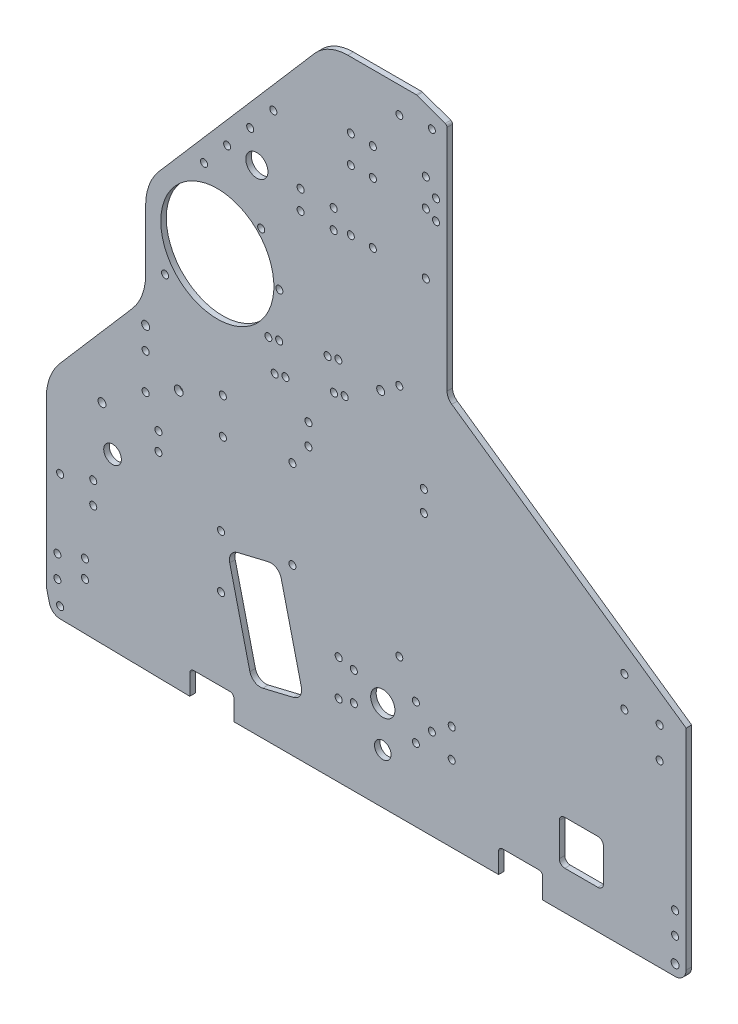
SolidWorks part; units mm, degrees
ref_plane "Front Plane" through (0, 0, 0) normal (0, 0, 1) x (1, 0, 0)
ref_plane "Top Plane" through (0, 0, 0) normal (0, 1, 0) x (1, 0, 0)
ref_plane "Right Plane" through (0, 0, 0) normal (1, 0, 0) x (0, 0, -1)
sketch "Sketch1" plane through (0, 0, 0) normal (0, 0, 1) x (1, 0, 0)
  line L0 (82.55, -20.32) -> (82.55, -6.35)
  line L2 (0, 0) -> (0, 157.48)
  line L4 (368.3, -20.32) -> (368.3, 106.68)
  line L5 (82.55, -6.35) -> (107.95, -6.35)
  line L6 (107.95, -6.35) -> (107.95, -20.32)
  line L7 (107.95, -20.32) -> (260.35, -20.32)
  line L8 (260.35, -20.32) -> (260.35, -6.35)
  line L9 (260.35, -6.35) -> (285.75, -6.35)
  line L10 (285.75, -6.35) -> (285.75, -20.32)
  line L11 (285.75, -20.32) -> (368.3, -20.32)
  line L12 (361.95, 12.7) -> (368.3, 12.7) construction
  line L13 (0, 0) -> (6.35, 0) construction
  line L14 (0.1896, -7.8901) -> (1.7771, -14.2401)
  line L15 (7.8295, -19.0491) -> (82.55, -20.32)
  line L16 (0, 0) -> (0, -6.35)
  line L17 (76.2, 128.905) -> (79.375, 128.905) construction
  line L18 (57.15, 118.5863) -> (101.6, 118.5862) construction
  line L19 (57.15, 118.5863) -> (57.15, 139.2238) construction
  line L20 (101.6, 118.5862) -> (101.6, 139.2237) construction
  line L21 (57.15, 139.2238) -> (101.6, 139.2237) construction
  line L22 (57.15, 118.5863) -> (101.6, 139.2237) construction
  line L23 (101.6, 118.5862) -> (57.15, 139.2238) construction
  line L25 (203.2, 59.805) -> (203.2, 194.805) construction
  line L26 (203.2, 194.805) -> (203.2, 329.805) construction
  line L27 (355.6, 332.105) -> (330.2, 332.105) construction
  line L28 (330.2, 332.105) -> (330.2, 217.805) construction
  line L29 (330.2, 217.805) -> (355.6, 217.805) construction
  line L30 (355.6, 217.805) -> (355.6, 332.105) construction
  line L31 (203.2, 344.805) -> (203.2, 194.805) construction
  line L32 (50.8, 332.105) -> (76.2, 332.105) construction
  line L33 (76.2, 332.105) -> (76.2, 217.805) construction
  line L34 (50.8, 217.805) -> (50.8, 332.105) construction
  line L35 (76.2, 217.805) -> (50.8, 217.805) construction
  line L36 (213.2, 344.805) -> (230.6638, 338.455)
  line L37 (203.2, 344.805) -> (161.925, 344.805)
  line L38 (203.2, 344.805) -> (213.2, 344.805)
  line L39 (348.5362, 344.805) -> (413.4623, 344.805)
  line L40 (348.5362, 344.805) -> (230.6638, 344.805) construction
  line L42 (161.925, 344.805) -> (0, 157.48)
  line L44 (230.6638, 338.455) -> (230.6638, 202.565)
  line L45 (230.6638, 202.565) -> (368.3, 106.68)
  line L46 (213.2, 344.805) -> (-141.0713, 344.805) construction
  circle A0 centre (6.35, 0) radius 2.032
  circle A1 centre (6.35, 12.7) radius 2.032
  circle A2 centre (361.95, 0) radius 2.032
  circle A3 centre (361.95, 12.7) radius 2.032
  arc A5 (1.7771, -14.2401) -> (7.8295, -19.0491) centre (7.9375, -12.7) ccw
  circle A6 centre (7.9375, -12.7) radius 2.032
  arc A7 (0, -6.35) -> (0.1896, -7.8901) centre (6.35, -6.35) ccw
  circle A8 centre (38.1, 78.105) radius 5.08
  circle A9 centre (76.2, 128.905) radius 2.54
  circle A10 centre (101.6, 118.5862) radius 2.032
  circle A11 centre (101.6, 139.2237) radius 2.032
  circle A12 centre (57.15, 139.2238) radius 2.032
  circle A13 centre (57.15, 118.5863) radius 2.032
  circle A15 centre (203.2, 59.805) radius 2
  circle A16 centre (203.2, 194.805) radius 2
  circle A17 centre (203.2, 329.805) radius 2
  circle A18 centre (63.5, 313.055) radius 2.032
  circle A20 centre (355.6, 332.105) radius 2.032
  circle A21 centre (330.2, 332.105) radius 2.032
  circle A22 centre (355.6, 217.805) radius 2.032
  circle A23 centre (330.2, 217.805) radius 2.032
  circle A24 centre (50.8, 332.105) radius 2.032
  circle A25 centre (76.2, 332.105) radius 2.032
  circle A26 centre (50.8, 217.805) radius 2.032
  circle A27 centre (76.2, 217.805) radius 2.032
  circle A28 centre (221.9319, 332.105) radius 2
  circle A29 centre (224.3138, 298.831) radius 2.032
  circle A30 centre (353.06, 100.7351) radius 2.032
  circle A31 centre (332.74, 115.9751) radius 2.032
  circle A32 centre (332.74, 98.1951) radius 2.032
  circle A33 centre (353.06, 82.9551) radius 2.032
  circle A34 centre (117.3562, 280.4276) radius 2.032
  circle A35 centre (104.0678, 265.0548) radius 2.032
  circle A36 centre (90.7795, 249.682) radius 2.032
  circle A38 centre (130.6445, 295.8004) radius 2.032
  circle A39 centre (68.326, 182.9237) radius 2.032
  circle A40 centre (224.3138, 287.401) radius 2.032
  point P82 (203.2, 344.805)
  point P83 (221.9319, 341.63)
  point P90 (368.3, 62.484)
  dimension "D6" = 4.064
  dimension "D10" = 6.35
  dimension "D11" = 4.064
  dimension "D17" = 38.1
  dimension "D27" = 4
  dimension "D31" = 4.064
  dimension "D32" = 41.275
  dimension "D36" = 4.064
  dimension "D47" = 39.624
  dimension "D48" = 4.064
  dimension "D25" = 5.08
  dimension "D26" = 4.064
  dimension "D52" = 4.064
  dimension "D65" = 4.064
  dimension "D69" = 10.16
  dimension "D2" = 127
  dimension "D3" = 13.97
  dimension "D4" = 25.4
  dimension "D5" = 152.4
  dimension "D7" = 12.7
  dimension "D8" = 6.35
  dimension "D9" = 20.32
  dimension "D12" = 12.7
  dimension "D13" = 1.5875
  dimension "D14" = 82.55
  dimension "D15" = 368.3
  dimension "D16" = 6.35
  dimension "D18" = 98.425
  dimension "D19" = 38.1
  dimension "D20" = 50.8
  dimension "D21" = 3.175
  dimension "D22" = 270
  dimension "D23" = 20.6375
  dimension "D24" = 44.45
  dimension "D28" = 135
  dimension "D29" = 12.7
  dimension "D30" = 15
  dimension "D33" = 63.5
  dimension "D34" = 27.4638
  dimension "D35" = 12.7
  dimension "D37" = 114.3
  dimension "D38" = 25.4
  dimension "D39" = 12.7
  dimension "D40" = 157.48
  dimension "D41" = 142.24
  dimension "D42" = 365.125
  dimension "D43" = 10
  dimension "D44" = 6.35
  dimension "D45" = 31.75
  dimension "D46" = 6.35
  dimension "D49" = 6.35
  dimension "D50" = 203.2
  dimension "D51" = 15.24
  dimension "D53" = 17.78
  dimension "D54" = 17.78
  dimension "D55" = 20.32
  dimension "D56" = 15.24
  dimension "D57" = 92.202
  dimension "D58" = 8.382
  dimension "D59" = 20.32
  dimension "D60" = 20.32
  dimension "D61" = 8.382
  dimension "D62" = 20.32
  dimension "D63" = 8.382
  dimension "D64" = 8.382
  dimension "D66" = 35.052
  dimension "D67" = 68.326
  dimension "D68" = 11.43
extrude "Boss-Extrude1" add sketch "Sketch1" along normal blind 3.175 contours L16 A7 L14 A5 L15 L2 A0 A1 A6 region at (171.4477, 119.565, 0)
fillet "Fillet1" radius 2.286 4 edges at (285.75, -6.35, 1.5875) (107.95, -6.35, 1.5875) (260.35, -6.35, 1.5875) (82.55, -6.35, 1.5875)
fillet "Fillet2" radius 6.35 1 edges at (230.6638, 202.565, 1.5875)
sketch "Sketch2" plane through (0, 0, 0) normal (0, 0, -1) x (-1, 0, 0)
  circle A0 centre (-100.5528, 71.086) radius 2.032 construction
  circle A1 centre (-100.5528, 40.606) radius 2.032 construction
  circle A2 centre (-22.225, 18.2025) radius 2.032 construction
  circle A3 centre (-22.225, 8.0425) radius 2.032 construction
  circle A4 centre (-100.5528, 71.086) radius 2.032
  circle A5 centre (-100.5528, 40.606) radius 2.032
  circle A6 centre (-22.225, 18.2025) radius 2.032
  circle A7 centre (-22.225, 8.0425) radius 2.032
extrude "Cut-Extrude1" cut sketch "Sketch2" against normal through all
fillet "Fillet3" radius 1.5875 2 edges at (230.6638, 338.455, 1.5875) (213.2, 344.805, 1.5875)
sketch "Sketch3" plane through (0, 0, 3.175) normal (0, 0, 1) x (1, 0, 0)
  line L0 (132.9524, 63.2646) -> (132.7215, 64.2281) construction
  line L1 (128.3814, 66.8897) -> (110.6828, 62.6472) construction
  line L2 (114.5132, 58.4237) -> (126.8822, 61.3887) construction
  line L3 (108.0212, 58.3071) -> (108.2522, 57.3436) construction
  line L4 (131.2006, 57.703) -> (140.0164, 20.9265) construction
  line L5 (144.0993, 16.7636) -> (132.9524, 63.2646) construction
  line L6 (108.2522, 57.3436) -> (119.3991, 10.8426) construction
  line L7 (121.1509, 16.4042) -> (112.3351, 53.1807) construction
  line L8 (119.3991, 10.8426) -> (119.6301, 9.8791) construction
  line L9 (144.3303, 15.8001) -> (144.0993, 16.7636) construction
  line L10 (137.8383, 15.6835) -> (125.4694, 12.7185) construction
  line L11 (123.9701, 7.2175) -> (141.6687, 11.4601) construction
  line L12 (132.9524, 63.2646) -> (132.7215, 64.2281)
  line L13 (128.3814, 66.8897) -> (110.6828, 62.6472)
  line L14 (114.5132, 58.4237) -> (126.8822, 61.3887)
  line L15 (108.0212, 58.3071) -> (108.2522, 57.3436)
  line L16 (131.2006, 57.703) -> (140.0164, 20.9265)
  line L17 (144.0993, 16.7636) -> (132.9524, 63.2646)
  line L18 (108.2522, 57.3436) -> (119.3991, 10.8426)
  line L19 (121.1509, 16.4042) -> (112.3351, 53.1807)
  line L20 (119.3991, 10.8426) -> (119.6301, 9.8791)
  line L21 (144.3303, 15.8001) -> (144.0993, 16.7636)
  line L22 (137.8383, 15.6835) -> (125.4694, 12.7185)
  line L23 (123.9701, 7.2175) -> (141.6687, 11.4601)
  line L24 (127.7894, 69.3598) -> (110.0908, 65.1172)
  line L25 (105.5512, 57.715) -> (105.7822, 56.7515)
  line L26 (105.7822, 56.7515) -> (116.9291, 10.2505)
  line L27 (116.9291, 10.2505) -> (117.16, 9.287)
  line L28 (124.5622, 4.7475) -> (142.2608, 8.99)
  line L29 (146.8003, 16.3922) -> (146.5694, 17.3557)
  line L30 (146.5694, 17.3557) -> (135.4225, 63.8567)
  line L31 (135.4225, 63.8567) -> (135.1915, 64.8202)
  line L32 (14.605, -0.1369) -> (103.7278, 32.3011) construction
  line L33 (14.605, -0.1369) -> (103.7278, 32.3011)
  line L34 (0, -6.35) -> (0, 157.48) construction
  line L35 (-39.6666, 74.7152) -> (103.7278, 126.9065) construction
  line L36 (26.9875, 46.9531) -> (26.9875, 59.6531) construction
  line L37 (107.95, -20.32) -> (260.35, -20.32) construction
  line L38 (64.5259, 92.5258) -> (64.5259, 102.9405) construction
  arc A0 (132.7215, 64.2281) -> (128.6308, 66.9403) centre (129.2206, 63.3889) ccw construction
  arc A1 (110.6828, 62.6472) -> (110.4377, 62.5791) centre (111.522, 59.1463) ccw construction
  arc A2 (128.6308, 66.9403) -> (128.3814, 66.8897) centre (129.2206, 63.3889) ccw construction
  arc A3 (110.4377, 62.5791) -> (108.0212, 58.3071) centre (111.522, 59.1463) ccw construction
  arc A4 (119.6301, 9.8791) -> (123.7207, 7.1669) centre (123.1309, 10.7183) ccw construction
  arc A5 (141.9139, 11.5281) -> (144.3303, 15.8001) centre (140.8295, 14.9609) ccw construction
  arc A6 (141.6687, 11.4601) -> (141.9139, 11.5281) centre (140.8295, 14.9609) ccw construction
  arc A7 (123.7207, 7.1669) -> (123.9701, 7.2175) centre (123.1309, 10.7183) ccw construction
  arc A8 (132.7215, 64.2281) -> (128.6308, 66.9403) centre (129.2206, 63.3889) ccw
  arc A9 (110.6828, 62.6472) -> (110.4377, 62.5791) centre (111.522, 59.1463) ccw
  arc A10 (128.6308, 66.9403) -> (128.3814, 66.8897) centre (129.2206, 63.3889) ccw
  arc A11 (110.4377, 62.5791) -> (108.0212, 58.3071) centre (111.522, 59.1463) ccw
  arc A12 (119.6301, 9.8791) -> (123.7207, 7.1669) centre (123.1309, 10.7183) ccw
  arc A13 (141.9139, 11.5281) -> (144.3303, 15.8001) centre (140.8295, 14.9609) ccw
  arc A14 (141.6687, 11.4601) -> (141.9139, 11.5281) centre (140.8295, 14.9609) ccw
  arc A15 (123.7207, 7.1669) -> (123.9701, 7.2175) centre (123.1309, 10.7183) ccw
  arc A16 (110.0908, 65.1172) -> (109.6726, 65.0012) centre (111.522, 59.1463) ccw
  arc A17 (109.6726, 65.0012) -> (105.5512, 57.715) centre (111.522, 59.1463) ccw
  arc A18 (117.16, 9.287) -> (124.1369, 4.6613) centre (123.1309, 10.7183) ccw
  arc A19 (124.1369, 4.6613) -> (124.5622, 4.7475) centre (123.1309, 10.7183) ccw
  arc A20 (142.2608, 8.99) -> (142.6789, 9.1061) centre (140.8295, 14.9609) ccw
  arc A21 (142.6789, 9.1061) -> (146.8003, 16.3922) centre (140.8295, 14.9609) ccw
  arc A22 (135.1915, 64.8202) -> (128.2147, 69.446) centre (129.2206, 63.3889) ccw
  arc A23 (128.2147, 69.446) -> (127.7894, 69.3598) centre (129.2206, 63.3889) ccw
  circle A26 centre (134.1438, 208.2281) radius 2.032 construction
  circle A33 centre (26.9875, 46.9531) radius 2.032
  circle A34 centre (26.9875, 59.6531) radius 2.032
  circle A35 centre (7.9375, 53.3031) radius 2.032
  circle A37 centre (32.0306, 100.8109) radius 31.75 construction
  circle A38 centre (32.0306, 100.8109) radius 2.286
  circle A39 centre (123.682, 233.4851) radius 2.032 construction
  circle A40 centre (64.5259, 102.9405) radius 2.032
  circle A41 centre (64.5259, 92.5258) radius 2.032
  circle A42 centre (134.1438, 208.2281) radius 2.032
  circle A43 centre (123.682, 233.4851) radius 2.032
  ellipse E0 centre (124.5974, 48.8487) end of major axis (128.5376, 61.3578) minor radius 6 (131.2006, 57.703) -> (126.8822, 61.3887) ccw construction
  ellipse E1 centre (122.2349, 48.2824) end of major axis (113.0518, 57.6456) minor radius 6 (114.5132, 58.4237) -> (112.3351, 53.1807) ccw construction
  ellipse E2 centre (127.7541, 25.2585) end of major axis (131.6942, 37.7675) minor radius 6 (121.1509, 16.4042) -> (125.4694, 12.7185) ccw construction
  ellipse E3 centre (130.1166, 25.8248) end of major axis (139.2998, 16.4616) minor radius 6 (137.8383, 15.6835) -> (140.0164, 20.9265) ccw construction
  ellipse E4 centre (124.5974, 48.8487) end of major axis (128.5376, 61.3578) minor radius 6 (131.2006, 57.703) -> (126.8822, 61.3887) ccw
  ellipse E5 centre (122.2349, 48.2824) end of major axis (131.4181, 38.9192) minor radius 6 (114.5132, 58.4237) -> (112.3351, 53.1807) ccw
  ellipse E6 centre (127.7541, 25.2585) end of major axis (123.8139, 12.7495) minor radius 6 (121.1509, 16.4042) -> (125.4694, 12.7185) ccw
  ellipse E7 centre (130.1166, 25.8248) end of major axis (139.2998, 16.4616) minor radius 6 (137.8383, 15.6835) -> (140.0164, 20.9265) ccw
  point P93 (26.9875, 53.3031)
  point P115 (32.0306, 100.8109)
  dimension "D3" = 63.5
  dimension "D4" = 4.572
  dimension "D8" = 4.064
  dimension "D2" = 88.9
  dimension "D5" = 7.9375
  dimension "D6" = 19.05
  dimension "D7" = 73.6231
  dimension "D9" = 12.7
  dimension "D10" = 10.4147
  dimension "D11" = 37.5384
  dimension "D12" = 45.5727
  dimension "D1" = 2.54
extrude "Cut-Extrude2" cut sketch "Sketch3" against normal through all contours A22 A23 L24 A16 A17 L25 L26 L27 A18 A19 L28 A20 A21 L29 L30 L31 A15 A12 L20 L18 L15 A11 A9 L13 A10 A8 L12 L17 L21 A13 A14 L23 | A12 A15 L23 A14 A13 L21 L17 L12 A8 A10 L13 A9 A11 L15 L18 L20 E7 L22 E6 L19 E5 L14 E4 L16 | L22 E7 L16 E4 L14 E5 L19 E6 | A38 | A41 | A40 | A35 | A34 | A33 | A43 | A42 region at (137.844, 39.8506, 3.175) region at (126.1758, 37.0536, 3.175) region at (128.1544, 68.6507, 3.175) region at (32.0306, 100.8109, 3.175) region at (64.5259, 102.9405, 3.175) region at (64.5259, 92.5258, 3.175)
sketch "Sketch4" plane through (0, 0, 3.175) normal (0, 0, 1) x (1, 0, 0)
  line L0 (57.15, 139.2238) -> (101.6, 139.2237) construction
  line L1 (168.275, 21.4312) -> (212.725, 21.4312) construction
  line L2 (168.275, 21.4312) -> (168.275, 42.0687) construction
  line L3 (168.275, 42.0687) -> (212.725, 42.0687) construction
  line L4 (212.725, 21.4312) -> (212.725, 42.0687) construction
  line L5 (168.275, 21.4312) -> (212.725, 42.0687) construction
  line L6 (168.275, 42.0687) -> (212.725, 21.4312) construction
  line L7 (57.15, 118.5863) -> (57.15, 139.2238) construction
  line L8 (107.95, -20.32) -> (260.35, -20.32) construction
  line L9 (193.675, 31.75) -> (177.005, 31.75) construction
  line L10 (190.5, 31.75) -> (193.675, 31.75) construction
  line L11 (6.35, 12.7) -> (361.95, 12.7) construction
  line L12 (107.95, -6.35) -> (107.95, -20.32) construction
  line L13 (193.675, 31.75) -> (220.6625, 31.75) construction
  line L14 (177.005, 23.4569) -> (177.005, 40.0431) construction
  line L15 (213.2, 44.805) -> (193.2, 44.805) construction
  line L16 (213.2, 44.805) -> (213.2, 344.805) construction
  line L17 (213.2, 344.805) -> (193.2, 344.805) construction
  line L18 (193.2, 44.805) -> (193.2, 344.805) construction
  line L19 (213.2, 44.805) -> (193.2, 344.805) construction
  line L20 (213.2, 344.805) -> (193.2, 44.805) construction
  line L21 (226.9319, 332.105) -> (226.9319, 31.75) construction
  line L22 (237.33, 40.0431) -> (233.3612, 40.0431) construction
  line L23 (237.33, 23.4569) -> (233.3612, 23.4569) construction
  circle A0 centre (168.275, 42.0687) radius 2.032
  circle A1 centre (212.725, 42.0687) radius 2.032
  circle A2 centre (212.725, 21.4312) radius 2.032
  circle A3 centre (168.275, 21.4312) radius 2.032
  circle A4 centre (193.675, 31.75) radius 6.985
  circle A7 centre (220.6625, 31.75) radius 14.2875 construction
  circle A8 centre (193.675, 31.75) radius 12.7 construction
  circle A9 centre (177.005, 40.0431) radius 2.032
  circle A10 centre (177.005, 23.4569) radius 2.032
  circle A11 centre (237.33, 40.0431) radius 2.032 construction
  circle A12 centre (237.33, 23.4569) radius 2.032 construction
  circle A13 centre (193.675, 8.4667) radius 4.7625
  circle A14 centre (221.9319, 31.75) radius 2.032
  circle A15 centre (221.9319, 31.75) radius 5 construction
  circle A16 centre (221.9319, 332.105) radius 5 construction
  circle A17 centre (233.3612, 23.4569) radius 2.032
  circle A18 centre (233.3612, 40.0431) radius 2.032
  point P0 (190.5, 31.75)
  point P26 (203.2, 194.805)
  point P38 (177.005, 31.75)
  dimension "D1" = 4.064
  dimension "D4" = 13.97
  dimension "D7" = 9.525
  dimension "D10" = 25.4
  dimension "D11" = 28.575
  dimension "D16" = 10
  dimension "D17" = 4.064
  dimension "D18" = 10
  dimension "D2" = 52.07
  dimension "D3" = 3.175
  dimension "D5" = 82.55
  dimension "D6" = 26.9875
  dimension "D8" = 20
  dimension "D9" = 300
  dimension "D12" = 16.67
  dimension "D13" = 16.5862
  dimension "D14" = 60.325
  dimension "D15" = 23.2833
  dimension "D19" = 3.9688
extrude "Cut-Extrude3" cut sketch "Sketch4" against normal through all
sketch "Sketch5" plane through (0, 0, 0) normal (0, 0, -1) x (-1, 0, 0)
  line L0 (-57.15, 223.5947) -> (-57.15, 165.3337)
  line L1 (-161.925, 344.805) -> (-52.7201, 218.4699) construction
  line L2 (-57.15, 165.3337) -> (0, 99.219)
  line L3 (0, -6.35) -> (0, 157.48) construction
  line L5 (-50.4199, 215.8089) -> (0, 157.48) construction
  line L6 (-57.15, 223.5947) -> (0, 157.48)
  line L7 (0, 157.48) -> (0, 99.219)
  line L8 (-361.95, -13.97) -> (-368.3, -13.97) construction
  line L9 (-361.95, -13.97) -> (-361.95, -20.32) construction
  line L10 (-285.75, -20.32) -> (-368.3, -20.32) construction
  line L11 (-368.3, -20.32) -> (-368.3, 106.68) construction
  circle A0 centre (-98.425, 208.2281) radius 32.5437
  circle A2 centre (-361.95, -13.97) radius 2.286
  dimension "D3" = 65.0875
  dimension "D7" = 4.572
  dimension "D1" = 38.1
  dimension "D2" = 57.15
  dimension "D4" = 41.275
  dimension "D5" = 41.275
  dimension "D6" = 6.35
extrude "Cut-Extrude5" cut sketch "Sketch5" against normal through all contours A0 | L7 L6 L0 L2 | A2 region at (28.575, 161.4068, 0) region at (98.425, 208.2281, 0)
fillet "Fillet4" radius 31.75 3 edges at (0, 99.219, 1.5875) (57.15, 165.3337, 1.5875) (57.15, 223.5947, 1.5875)
sketch "Sketch6" plane through (0, 0, 3.175) normal (0, 0, 1) x (1, 0, 0)
  line L0 (285.75, -20.32) -> (368.3, -20.32) construction
  line L1 (298.45, 27.305) -> (317.5, 27.305)
  line L2 (295.275, 24.13) -> (295.275, 5.08)
  line L3 (298.45, 1.905) -> (317.5, 1.905)
  line L4 (320.675, 24.13) -> (320.675, 5.08)
  line L5 (295.275, 27.305) -> (320.675, 1.905) construction
  line L6 (295.275, 1.905) -> (320.675, 27.305) construction
  line L7 (368.3, -20.32) -> (368.3, 106.68) construction
  arc A0 (295.275, 5.08) -> (298.45, 1.905) centre (298.45, 5.08) ccw
  arc A1 (317.5, 1.905) -> (320.675, 5.08) centre (317.5, 5.08) ccw
  arc A2 (317.5, 27.305) -> (320.675, 24.13) centre (317.5, 24.13) cw
  arc A3 (298.45, 27.305) -> (295.275, 24.13) centre (298.45, 24.13) ccw
  point P0 (307.975, 14.605)
  dimension "D2" = 3.175
  dimension "D1" = 25.4
  dimension "D3" = 22.225
  dimension "D4" = 47.625
extrude "Cut-Extrude6" cut sketch "Sketch6" against normal through all
fillet "Fillet5" radius 25.4 1 edges at (161.925, 344.805, 1.5875)
sketch "Sketch8" plane through (0, 0, 0) normal (0, 0, -1) x (-1, 0, 0)
  line L0 (-230.6638, 337.343) -> (-230.6638, 205.8802) construction
  line L1 (-230.6638, 255.905) -> (-175.26, 255.905) construction
  line L2 (-175.26, 255.905) -> (-175.26, 306.705) construction
  line L3 (-175.26, 306.705) -> (-230.6638, 306.705) construction
  line L4 (-173.5432, 344.805) -> (-212.9203, 344.805) construction
  line L7 (-107.95, -20.32) -> (-260.35, -20.32) construction
  circle A0 centre (-218.44, 290.83) radius 3.9687
  circle A1 centre (-218.44, 290.83) radius 2.032
  circle A2 centre (218.44, 265.7972) radius 3.9687
  circle A3 centre (218.44, 265.7972) radius 2.032
  circle A4 centre (-205.74, 290.83) radius 3.9687
  circle A5 centre (-205.74, 290.83) radius 2.032
  circle A6 centre (-187.96, 290.83) radius 3.9687
  circle A7 centre (-187.96, 290.83) radius 2.032
  circle A8 centre (-187.96, 306.705) radius 2.032
  circle A9 centre (-175.26, 290.83) radius 3.9687
  circle A10 centre (-175.26, 290.83) radius 2.032
  circle A11 centre (-205.74, 306.705) radius 2.032
  circle A13 centre (-205.74, 255.905) radius 2.032
  circle A14 centre (-187.96, 255.905) radius 2.032
  circle A16 centre (-218.44, 306.705) radius 2.032
  circle A17 centre (-175.26, 306.705) radius 2.032
  circle A18 centre (-175.26, 255.905) radius 2.032
  circle A19 centre (-218.44, 255.905) radius 2.032
  circle A20 centre (-218.44, 306.705) radius 3.9687
  circle A21 centre (-205.74, 306.705) radius 3.9687
  circle A22 centre (-175.26, 306.705) radius 3.9687
  circle A23 centre (-218.44, 255.905) radius 3.9687
  circle A24 centre (-205.74, 255.905) radius 3.9687
  circle A25 centre (-187.96, 255.905) radius 3.9687
  circle A26 centre (-175.26, 255.905) radius 3.9687
  circle A27 centre (-187.96, 306.705) radius 3.9687
  dimension "D1" = 7.9375
  dimension "D7" = 4.064
  dimension "D13" = 12.2237
  dimension "D2" = 12.2237
  dimension "D3" = 12.7
  dimension "D4" = 17.78
  dimension "D5" = 12.7
  dimension "D6" = 88.9
  dimension "D8" = 38.1
  dimension "D9" = 17.78
  dimension "D10" = 12.7
  dimension "D11" = 55.4037
  dimension "D12" = 12.7
  dimension "D14" = 311.15
extrude "Cut-Extrude7" cut sketch "Sketch8" against normal through all contours A16 | A17 | A18 | A19 | A8 | A14 | A1 | A7 | A10 region at (218.44, 306.705, 0) region at (175.26, 306.705, 0) region at (175.26, 255.905, 0) region at (218.44, 255.905, 0)
sketch "Sketch10" plane through (0, 0, 3.175) normal (0, 0, 1) x (1, 0, 0)
  circle A4 centre (141.6425, 74.6844) radius 2.032 construction
  circle A5 centre (141.6425, 125.4844) radius 2.032 construction
  circle A6 centre (141.6425, 74.6844) radius 2.032
  circle A7 centre (141.6425, 125.4844) radius 2.032
extrude "Cut-Extrude8" cut sketch "Sketch10" against normal through all
fillet "Fillet6" radius 6.35 1 edges at (368.3, -20.32, 1.5875)
sketch "Sketch11" plane through (0, 0, 3.175) normal (0, 0, 1) x (1, 0, 0)
  ellipse E4 centre (150.8814, 138.43) end of major axis (150.8814, 140.462) minor radius 2.032
  ellipse E5 centre (150.8814, 150.495) end of major axis (150.8814, 152.527) minor radius 2.032
  ellipse E6 centre (217.3024, 150.495) end of major axis (217.3024, 152.527) minor radius 2.032
  ellipse E7 centre (217.3024, 138.43) end of major axis (217.3024, 140.462) minor radius 2.032
extrude "Cut-Extrude9" cut sketch "Sketch11" against normal through all
sketch "Sketch12" plane through (0, 0, 0) normal (0, 0, -1) x (-1, 0, 0)
  line L0 (-173.5432, 344.805) -> (-212.9203, 344.805) construction
  circle A0 centre (-165.4175, 264.635) radius 2.032
  circle A1 centre (-203.2, 329.805) radius 2 construction
  circle A2 centre (-165.4175, 253.5225) radius 2.032
  circle A3 centre (-146.3675, 253.5225) radius 2.032
  circle A4 centre (-146.3675, 264.635) radius 2.032
  dimension "D1" = 80.17
  dimension "D2" = 4.064
  dimension "D3" = 37.7825
  dimension "D4" = 11.1125
  dimension "D5" = 19.05
extrude "Cut-Extrude10" cut sketch "Sketch12" against normal through all
sketch "Sketch14" plane through (0, 0, 0) normal (0, 0, -1) x (-1, 0, 0)
  line L0 (-130.6445, 295.8004) -> (-121.1847, 263.6885) construction
  line L1 (-121.1847, 263.6885) -> (-90.7795, 249.682) construction
  line L2 (-154.3272, 336.0154) -> (-64.88, 232.5373) construction
  line L4 (-118.517, 269.4796) -> (-115.3937, 261.0208) construction
  line L5 (-118.517, 269.4796) -> (-126.9758, 266.3562) construction
  line L6 (-126.9758, 266.3562) -> (-123.8524, 257.8974) construction
  line L7 (-115.3937, 261.0208) -> (-123.8524, 257.8974) construction
  line L8 (-118.517, 269.4796) -> (-123.8524, 257.8974) construction
  line L9 (-126.9758, 266.3562) -> (-115.3937, 261.0208) construction
  circle A0 centre (-121.1847, 263.6885) radius 6.376
  dimension "D1" = 22.225
  dimension "D2" = 9.017
extrude "Cut-Extrude11" cut sketch "Sketch14" against normal through all
sketch "Sketch15" plane through (0, 0, 3.175) normal (0, 0, 1) x (1, 0, 0)
  line L1 (27.1508, 77.7471) -> (81.7263, 77.7471) construction
  line L2 (57.15, 139.2238) -> (57.15, 151.9238) construction
  line L3 (27.1508, 77.7471) -> (52.3291, 153.5255) construction
  line L4 (56.0505, 156.8833) -> (192.439, 187.1199) construction
  circle A0 centre (27.1508, 77.7471) radius 2.159 construction
  circle A1 centre (27.1508, 77.7471) radius 2.159 construction
  circle A2 centre (57.15, 139.2238) radius 2.032 construction
  circle A3 centre (57.15, 139.2238) radius 2.032 construction
  circle A4 centre (57.15, 151.9238) radius 2.286
  circle A5 centre (192.439, 187.1199) radius 2.286
  circle A6 centre (57.15, 151.9238) radius 5.08 construction
  arc A9 (163.8737, 173.6806) -> (164.5125, 170.7993) centre (165.557, 172.5423) ccw construction
  arc A10 (173.4398, 172.7784) -> (172.801, 175.6597) centre (171.7565, 173.9167) ccw construction
  arc A11 (172.801, 175.6597) -> (173.4398, 172.7784) centre (171.7565, 173.9167) ccw construction
  arc A12 (164.5125, 170.7993) -> (163.8737, 173.6806) centre (165.557, 172.5423) ccw construction
  arc A13 (169.1589, 192.0883) -> (169.7976, 189.2071) centre (168.1143, 190.3453) ccw construction
  arc A14 (169.7976, 189.2071) -> (169.1589, 192.0883) centre (168.1143, 190.3453) ccw construction
  arc A15 (160.2316, 190.1092) -> (160.8704, 187.2279) centre (161.9149, 188.9709) ccw construction
  arc A16 (160.8704, 187.2279) -> (160.2316, 190.1092) centre (161.9149, 188.9709) ccw construction
  arc A17 (129.7766, 166.1214) -> (130.4154, 163.2402) centre (131.4599, 164.9832) ccw construction
  arc A18 (139.3426, 165.2193) -> (138.7039, 168.1005) centre (137.6593, 166.3576) ccw construction
  arc A19 (138.7039, 168.1005) -> (139.3426, 165.2193) centre (137.6593, 166.3576) ccw construction
  arc A20 (130.4154, 163.2402) -> (129.7766, 166.1214) centre (131.4599, 164.9832) ccw construction
  arc A21 (135.7005, 181.6479) -> (135.0617, 184.5292) centre (134.0172, 182.7862) ccw construction
  arc A22 (135.0617, 184.5292) -> (135.7005, 181.6479) centre (134.0172, 182.7862) ccw construction
  arc A23 (126.1345, 182.55) -> (126.7732, 179.6688) centre (127.8177, 181.4118) ccw construction
  arc A24 (126.7732, 179.6688) -> (126.1345, 182.55) centre (127.8177, 181.4118) ccw construction
  arc A25 (163.8737, 173.6806) -> (164.5125, 170.7993) centre (165.557, 172.5423) ccw
  arc A26 (173.4398, 172.7784) -> (172.801, 175.6597) centre (171.7565, 173.9167) ccw
  arc A27 (172.801, 175.6597) -> (173.4398, 172.7784) centre (171.7565, 173.9167) ccw
  arc A28 (164.5125, 170.7993) -> (163.8737, 173.6806) centre (165.557, 172.5423) ccw
  arc A29 (169.1589, 192.0883) -> (169.7976, 189.2071) centre (168.1143, 190.3453) ccw
  arc A30 (169.7976, 189.2071) -> (169.1589, 192.0883) centre (168.1143, 190.3453) ccw
  arc A31 (160.2316, 190.1092) -> (160.8704, 187.2279) centre (161.9149, 188.9709) ccw
  arc A32 (160.8704, 187.2279) -> (160.2316, 190.1092) centre (161.9149, 188.9709) ccw
  arc A33 (129.7766, 166.1214) -> (130.4154, 163.2402) centre (131.4599, 164.9832) ccw
  arc A34 (139.3426, 165.2193) -> (138.7039, 168.1005) centre (137.6593, 166.3576) ccw
  arc A35 (138.7039, 168.1005) -> (139.3426, 165.2193) centre (137.6593, 166.3576) ccw
  arc A36 (130.4154, 163.2402) -> (129.7766, 166.1214) centre (131.4599, 164.9832) ccw
  arc A37 (135.7005, 181.6479) -> (135.0617, 184.5292) centre (134.0172, 182.7862) ccw
  arc A38 (135.0617, 184.5292) -> (135.7005, 181.6479) centre (134.0172, 182.7862) ccw
  arc A39 (126.1345, 182.55) -> (126.7732, 179.6688) centre (127.8177, 181.4118) ccw
  arc A40 (126.7732, 179.6688) -> (126.1345, 182.55) centre (127.8177, 181.4118) ccw
  dimension "D2" = 4.572
  dimension "D6" = 10.16
  dimension "D1" = 12.7
  dimension "D3" = 139.7
  dimension "D4" = 12.5
extrude "Cut-Extrude12" cut sketch "Sketch15" against normal through all
sketch "Sketch16" plane through (0, 0, 3.175) normal (0, 0, 1) x (1, 0, 0)
  circle A0 centre (98.425, 208.2281) radius 34.925 construction
  circle A1 centre (98.425, 208.2281) radius 34.925
  circle A2 centre (98.425, 208.2281) radius 36.195
  dimension "D1" = 1.27
